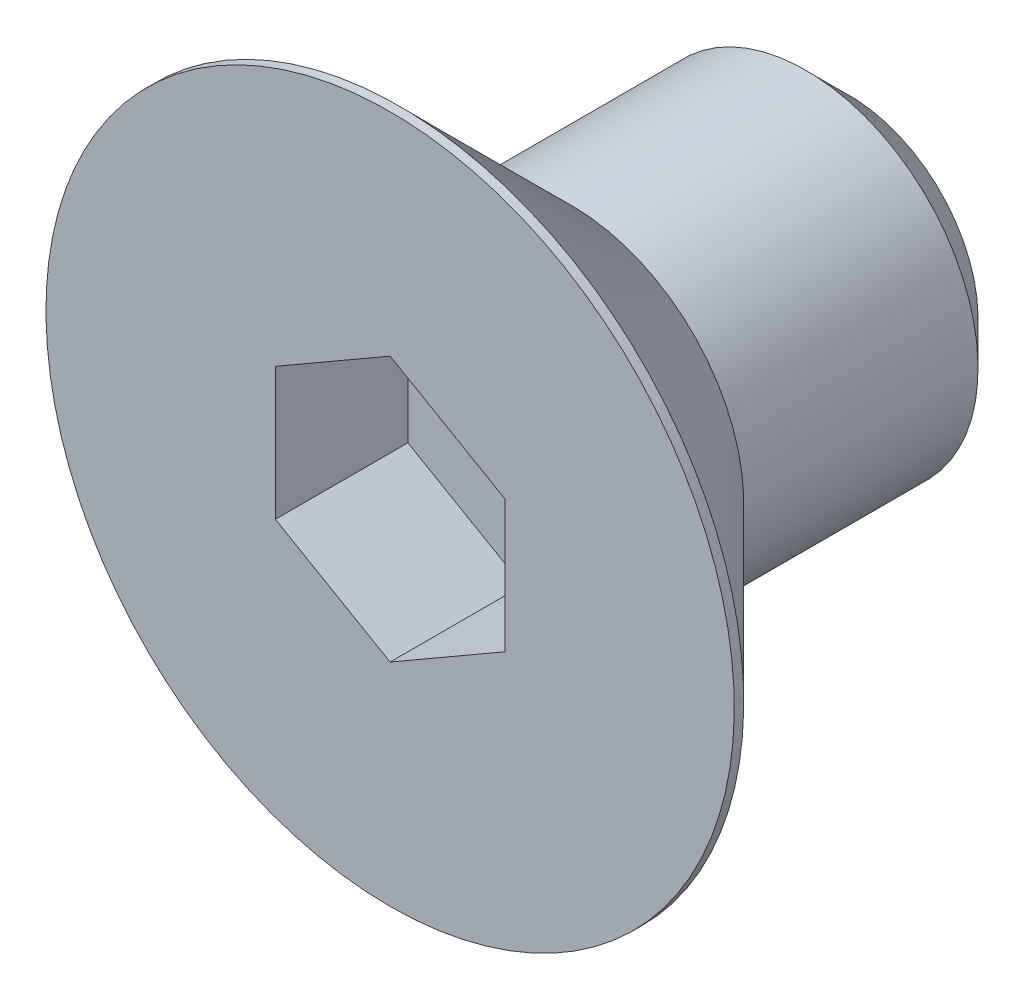
SolidWorks part; units mm, degrees
material "Chrome Stainless Steel"
ref_plane "Front" through (0, 0, 0) normal (0, 0, 1) x (1, 0, 0)
ref_plane "Top" through (0, 0, 0) normal (0, 1, 0) x (1, 0, 0)
ref_plane "Right" through (0, 0, 0) normal (1, 0, 0) x (0, 0, -1)
sketch "Sketch11" plane through (0, 0, 0) normal (1, 0, 0) x (0, 0, -1)
  line L0 (-4, 6) -> (4, 6) construction
  line L5 (-4, 6) -> (-4, -6) construction
  line L6 (4, 3) -> (4, -3) construction
  line L7 (-3.99, 2) -> (-3.99, -2) construction
  line L8 (3.9375, 3.1083) -> (4.9375, 3.1083) construction
  line L9 (4.9375, 3.1083) -> (4.4375, 2.2422) construction
  line L10 (4.4375, 2.2422) -> (3.9375, 3.1083) construction
  line L11 (4.375, 2.3505) -> (4.5, 2.3505) construction
  line L12 (4.4375, 2.3505) -> (4.4375, 2.2422) construction
  line L13 (3.9688, 3.0541) -> (4.9063, 3.0541) construction
  line L14 (4.4375, 3.1083) -> (4.4375, 3) construction
  line L15 (4, 3) -> (4.875, 3) construction
  line L17 (-3.835, 6) -> (2.165, 0) construction
  line L18 (2.165, 0) -> (-3.835, -6) construction
  point P3 (-0.7, 6)
  point P8 (0, 6)
  point P21 (4.4375, 3.0541)
  point P26 (-4, 0)
  point P28 (-3.99, 0)
  point P29 (4, 0)
  dimension "Length" = 8
  dimension "Head Diameter" = 12
  dimension "Thread Major Diameter" = 6
  dimension "Head Height" = 3.3
  dimension "Drive Size" = 4
  dimension "Thread Pitch" = 1
  dimension "D1" = 0.125
  dimension "D2" = 0.01
  dimension "D3" = 0.165
  dimension "Countersink Angle" = 90
sketch "Sketch1" plane through (0, 0, 0) normal (1, 0, 0) x (0, 0, -1)
  line L2 (-0.7, 3) -> (4, 3)
  line L3 (4, 3) -> (4, 0)
  line L4 (-1.69, 3) -> (-1.69, 0)
  line L5 (-0.7, 3) -> (-1.69, 3)
  line L6 (-4, 6) -> (-4, -6) construction
  line L7 (4, 3) -> (4, -3) construction
  line L8 (-1.69, 0) -> (4, 0)
  dimension "D1" = 2.31
revolve "Revolve1" add sketch "Sketch1" angle 360 mid plane about L8
chamfer "Chamfer1" distance 0.75 angle 45 1 edges at (0, -3, -4)
sketch "Sketch7" plane through (0, 0, 0) normal (1, 0, 0) x (0, 0, -1)
  line L2 (-4, 6) -> (-3.835, 6)
  line L5 (-0.7, 2.865) -> (-0.7, 0)
  line L6 (-4, 6) -> (-4, 0)
  line L8 (-4, 6) -> (-4, -6) construction
  line L9 (-4, 0) -> (-0.7, 0)
  line L12 (-3.835, 6) -> (-0.7, 2.865)
  line L13 (-3.835, 6) -> (2.165, 0) construction
revolve "Revolve2" add sketch "Sketch7" angle 360 mid plane about L9 region at (0, 2.3546, 2.5497)
ref_plane "Plane1" through (0, 0, 0.7) normal (0, 0, 1) x (1, 0, 0)
sketch "Sketch5" plane through (0, 0, 4) normal (0, 0, 1) x (1, 0, 0)
  line L1 (2, -1.1547) -> (2, 1.1547)
  line L2 (2, 1.1547) -> (0, 2.3094)
  line L3 (0, 2.3094) -> (-2, 1.1547)
  line L4 (-2, 1.1547) -> (-2, -1.1547)
  line L5 (-2, -1.1547) -> (0, -2.3094)
  line L6 (0, -2.3094) -> (2, -1.1547)
  circle A0 centre (0, 0) radius 2 construction
extrude "Cut-Extrude2" cut sketch "Sketch5" against normal blind 2.31
sketch "Sketch6" plane through (0, 0, 4) normal (0, 0, -1) x (-1, 0, 0)
  circle A0 centre (0, 0) radius 2.3094
extrude "Cut-Extrude3" [suppressed] cut sketch "Sketch6" along normal blind 2.31 draft 45
sketch "Sketch12" [suppressed] plane through (0, 0, -4) normal (0, 0, -1) x (-1, 0, 0)
  circle A0 centre (0, 0) radius 3 construction
  circle A1 centre (0, 0) radius 3
curve "Helix/Spiral1" [suppressed] pitch 1 height 8 turns 8
sketch "Sketch13" [suppressed] plane through (0, 0, 0) normal (1, 0, 0) x (0, 0, -1)
  line L0 (3.9688, 3.0541) -> (4.9063, 3.0541)
  line L1 (4.9063, 3.0541) -> (4.5, 2.3505)
  line L2 (4.5, 2.3505) -> (4.375, 2.3505)
  line L3 (4.375, 2.3505) -> (3.9688, 3.0541)
sweep "Cut-Sweep1" [suppressed] cut profiles "Sketch13" path "Helix/Spiral1"
combine bodies "Combine1" [suppressed] operation type add bodies to combine 113 127
equation "\"D1@Chamfer1\"=\"Thread Pitch@Sketch11\" * .75"
equation "\"D1@Cut-Extrude2\"= \"Head Height@Sketch11\" * .7"
equation "\"D1@Cut-Extrude3\" = \"D1@Cut-Extrude2\""
equation "\"D1@Sketch11\"=\"Thread Pitch@Sketch11\"/8"
equation "\"D3@Sketch11\"=\"Head Height@Sketch11\"*.05"
equation "\"D4@Helix/Spiral1\"=\"Thread Pitch@Sketch11\""
equation "\"D1@Sketch1\"=\"Head Height@Sketch11\"*.7"
equation "\"D3@Helix/Spiral1\"=\"Length@Sketch11\""
